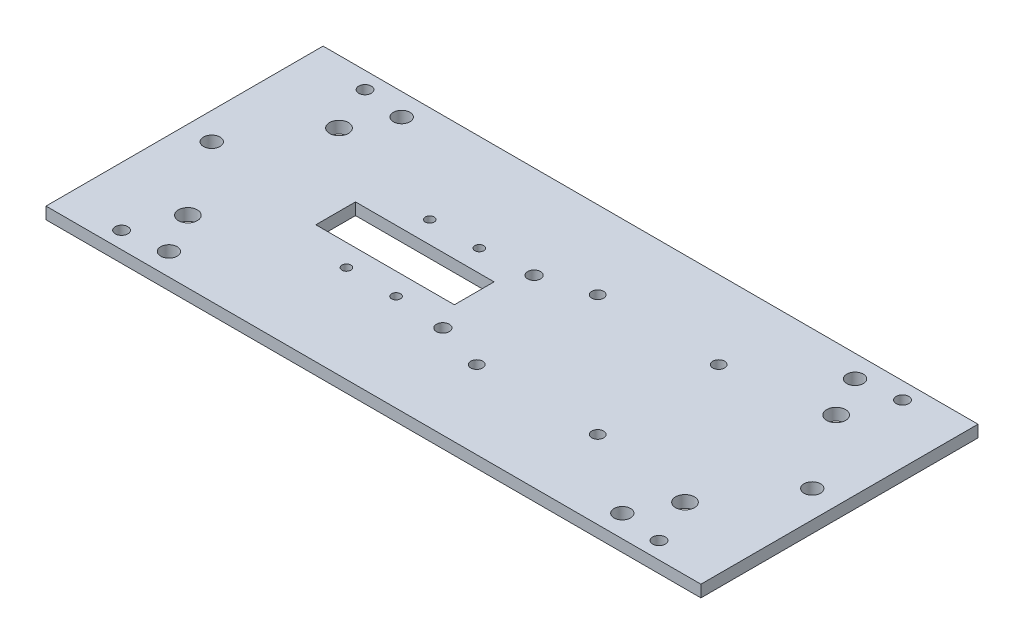
SolidWorks part; units mm, degrees
material "Thornel VCB-20 Carbon Cloth"
ref_plane "Front Plane" through (0, 0, 0) normal (0, 0, 1) x (1, 0, 0)
ref_plane "Top Plane" through (0, 0, 0) normal (0, 1, 0) x (1, 0, 0)
ref_plane "Right Plane" through (0, 0, 0) normal (1, 0, 0) x (0, 0, -1)
sketch "Sketch1" plane through (0, 0, 0) normal (0, 1, 0) x (1, 0, 0)
  line L0 (82.55, -34.925) -> (82.55, 34.925)
  line L1 (82.55, -34.925) -> (-82.55, -34.925)
  line L2 (82.55, 34.925) -> (-82.55, 34.925)
  line L3 (-82.55, -34.925) -> (-82.55, 34.925)
  line L4 (82.55, -34.925) -> (-82.55, 34.925) construction
  line L5 (82.55, 34.925) -> (-82.55, -34.925) construction
  point P1 (0, 0)
  dimension "D1" = 165.1
  dimension "D2" = 69.85
extrude "Boss-Extrude1" add sketch "Sketch1" along normal blind 3
sketch "Sketch6" plane through (0, 0, 0) normal (0, -1, 0) x (1, 0, 0)
  line L0 (-82.55, -34.925) -> (-82.55, 34.925) construction
  line L1 (-44.45, 5) -> (-9.525, 5)
  line L2 (-44.45, 5) -> (-44.45, -5)
  line L3 (-44.45, -5) -> (-9.525, -5)
  line L4 (-9.525, 5) -> (-9.525, -5)
  line L5 (-5.925, -11.501) -> (-63.925, -11.501) construction
  line L6 (-5.925, -11.501) -> (-5.925, 11.501) construction
  line L7 (-5.925, 11.501) -> (-63.925, 11.501) construction
  line L8 (-63.925, -11.501) -> (-63.925, 11.501) construction
  line L9 (-5.925, -11.501) -> (-63.925, 11.501) construction
  line L10 (-5.925, 11.501) -> (-63.925, -11.501) construction
  circle A0 centre (6.35, 15.25) radius 1.5
  circle A1 centre (36.85, 15.25) radius 1.5
  circle A2 centre (6.35, -15.25) radius 1.5
  circle A3 centre (36.85, -15.25) radius 1.5
  circle A4 centre (-63.925, 11.501) radius 1.625 construction
  circle A5 centre (-5.925, 11.501) radius 1.625
  circle A6 centre (-5.925, -11.501) radius 1.625
  circle A7 centre (-63.925, -11.501) radius 1.625 construction
  point P8 (-9.525, 0)
  point P18 (-34.925, 0)
  dimension "D5" = 3
  dimension "D6" = 3
  dimension "D7" = 3
  dimension "D8" = 3
  dimension "D18" = 3.25
  dimension "D1" = 34.925
  dimension "D2" = 10
  dimension "D3" = 38.1
  dimension "D4" = 30.5
  dimension "D9" = 30.5
  dimension "D10" = 30.5
  dimension "D11" = 15.25
  dimension "D12" = 6.35
  dimension "D13" = 15.25
  dimension "D14" = 15.25
  dimension "D15" = 15.25
  dimension "D16" = 23.002
  dimension "D17" = 58
  dimension "D19" = 47.625
  dimension "D20" = 0
extrude "Cut-Extrude1" cut sketch "Sketch6" against normal up to next contours A4 | L4 L1 L2 L3 A4 | A6 | A2 | A3 | A1 | A0 | A7 | A5 region at (-26.9875, 0, 0) region at (6.35, 0, 15.25) region at (36.85, 0, 15.25) region at (6.35, 0, -15.25) region at (36.85, 0, -15.25) region at (-5.925, 0, -11.501)
sketch "Sketch7" plane through (0, 3, 0) normal (0, 1, 0) x (1, 0, 0)
  line L0 (-82.55, 34.925) -> (-82.55, -34.925) construction
  line L1 (82.55, -34.925) -> (82.55, 34.925) construction
  line L2 (-82.55, -34.925) -> (82.55, -34.925) construction
  line L3 (82.55, 34.925) -> (-82.55, 34.925) construction
  circle A0 centre (-77.47, 29.845) radius 1.5
  circle A1 centre (-77.47, -29.845) radius 1.5
  circle A2 centre (77.47, -29.845) radius 1.5
  circle A3 centre (77.47, 29.845) radius 1.5
  dimension "D9" = 3
  dimension "D10" = 3
  dimension "D11" = 3
  dimension "D12" = 3
  dimension "D1" = 5.08
  dimension "D2" = 5.08
  dimension "D3" = 5.08
  dimension "D4" = 5.08
  dimension "D5" = 5.08
  dimension "D6" = 5.08
  dimension "D7" = 5.08
  dimension "D8" = 5.08
sketch "Sketch8" plane through (0, 3, 0) normal (0, 1, 0) x (1, 0, 0)
  line L0 (-82.55, -34.925) -> (82.55, -34.925) construction
  line L1 (-82.55, 34.925) -> (-82.55, -34.925) construction
  line L2 (82.55, -34.925) -> (82.55, 34.925) construction
  line L3 (82.55, 34.925) -> (-82.55, 34.925) construction
  circle A0 centre (-62.6618, -19.05) radius 2.3813
  circle A1 centre (-62.6618, 19.05) radius 2.3813
  circle A2 centre (62.6618, 19.05) radius 2.3813
  circle A3 centre (62.6618, -19.05) radius 2.3813
  dimension "D1" = 4.7625
  dimension "D4" = 4.7625
  dimension "D5" = 4.7625
  dimension "D6" = 4.7625
  dimension "D2" = 15.875
  dimension "D3" = 19.8882
  dimension "D7" = 19.8882
  dimension "D8" = 19.8882
  dimension "D9" = 19.8882
  dimension "D10" = 15.875
  dimension "D11" = 15.875
  dimension "D12" = 15.875
extrude "Cut-Extrude3" cut sketch "Sketch8" against normal up to next
sketch "Sketch9" plane through (0, 3, 0) normal (0, 1, 0) x (1, 0, 0)
  line L0 (-82.55, 34.925) -> (-82.55, -34.925) construction
  line L1 (82.55, -34.925) -> (82.55, 34.925) construction
  circle A0 centre (-75.692, 0) radius 2.0828
  circle A1 centre (75.692, 0) radius 2.0828
  dimension "D1" = 6.858
  dimension "D2" = 6.858
extrude "Cut-Extrude5" cut sketch "Sketch9" against normal blind 5.08
sketch "Sketch10" plane through (0, 3, 0) normal (0, 1, 0) x (1, 0, 0)
  line L0 (-82.55, -34.925) -> (82.55, -34.925) construction
  line L1 (82.55, 34.925) -> (-82.55, 34.925) construction
  circle A0 centre (0, -29.337) radius 2.0828
  circle A1 centre (0, 29.337) radius 2.0828
  circle A2 centre (57.15, -29.337) radius 2.0828
  circle A3 centre (57.15, 29.337) radius 2.0828
  circle A4 centre (-57.15, -29.337) radius 2.0828
  circle A5 centre (-57.15, 29.337) radius 2.0828
  dimension "D1" = 5.588
  dimension "D2" = 5.588
  dimension "D3" = 2
  dimension "D4" = 2
extrude "Cut-Extrude6" cut sketch "Sketch10" against normal blind 5.08 contours A5 | A2 | A3 | A4 region at (57.15, 3, 29.337) region at (57.15, 3, -29.337) region at (-57.15, 3, 29.337) region at (-57.15, 3, -29.337)
sketch "Sketch11" plane through (0, 3, 0) normal (0, 1, 0) x (1, 0, 0)
  line L1 (-18.7375, 10.5) -> (-31.2375, 10.5) construction
  line L2 (-18.7375, 10.5) -> (-18.7375, -10.5) construction
  line L3 (-18.7375, -10.5) -> (-31.2375, -10.5) construction
  line L4 (-31.2375, 10.5) -> (-31.2375, -10.5) construction
  line L5 (-18.7375, 10.5) -> (-31.2375, -10.5) construction
  line L6 (-18.7375, -10.5) -> (-31.2375, 10.5) construction
  line L7 (-9.525, 5) -> (-44.45, 5) construction
  circle A0 centre (-31.2375, 10.5) radius 1.125
  circle A1 centre (-18.7375, 10.5) radius 1.125
  circle A2 centre (-18.7375, -10.5) radius 1.125
  circle A3 centre (-31.2375, -10.5) radius 1.125
  point P0 (-24.9875, 0)
  point P9 (-26.9875, 5)
  dimension "D4" = 2.25
  dimension "D5" = 2.25
  dimension "D6" = 2.25
  dimension "D7" = 2.25
  dimension "D1" = 12.5
  dimension "D2" = 21
  dimension "D3" = 2
extrude "Cut-Extrude7" cut sketch "Sketch11" against normal blind 41.91
sketch "Sketch12" plane through (0, 0, 0) normal (0, -1, 0) x (1, 0, 0)
  line L0 (-24.5963, 23.3735) -> (-5.5463, 23.3735) construction
  line L1 (-24.5963, 24.5641) -> (-5.5463, 24.5641)
  line L2 (-24.5963, 24.5641) -> (-24.5963, 22.1829)
  line L3 (-24.5963, 22.1829) -> (-5.5463, 22.1829)
  line L4 (-5.5463, 24.5641) -> (-5.5463, 22.1829)
  line L5 (-15.0713, 24.5641) -> (-15.0713, 22.1829)
  line L6 (0.8037, 24.5641) -> (0.8037, 22.1829)
  line L7 (0.8037, 24.5641) -> (19.8537, 24.5641)
  line L8 (19.8537, 24.5641) -> (19.8537, 22.1829)
  line L9 (0.8037, 22.1829) -> (19.8537, 22.1829)
  line L10 (26.2037, 24.5641) -> (26.2037, 22.1829)
  line L11 (26.2037, 24.5641) -> (45.2537, 24.5641)
  line L12 (45.2537, 24.5641) -> (45.2537, 22.1829)
  line L13 (26.2037, 22.1829) -> (45.2537, 22.1829)
  line L14 (0.8037, 9.3241) -> (0.8037, 6.9429)
  line L15 (0.8037, 9.3241) -> (19.8537, 9.3241)
  line L16 (19.8537, 9.3241) -> (19.8537, 6.9429)
  line L17 (0.8037, 6.9429) -> (19.8537, 6.9429)
  line L18 (26.2037, 9.3241) -> (26.2037, 6.9429)
  line L19 (26.2037, 9.3241) -> (45.2537, 9.3241)
  line L20 (45.2537, 9.3241) -> (45.2537, 6.9429)
  line L21 (26.2037, 6.9429) -> (45.2537, 6.9429)
  line L22 (-24.5963, 9.3241) -> (-24.5963, 6.9429)
  line L23 (-24.5963, 9.3241) -> (-5.5463, 9.3241)
  line L24 (-5.5463, 9.3241) -> (-5.5463, 6.9429)
  line L25 (-24.5963, 6.9429) -> (-5.5463, 6.9429)
  line L26 (-24.5963, 24.5641) -> (0.8037, 24.5641) construction
  line L27 (-71.2714, 9.2531) -> (-61.3765, 9.2531)
  line L28 (-24.5963, -24.8071) -> (0.8037, -24.8071) construction
  line L29 (-24.5963, -23.6165) -> (-5.5463, -23.6165) construction
  line L30 (-24.5963, -7.1859) -> (-5.5463, -7.1859)
  line L31 (-5.5463, -9.5671) -> (-5.5463, -7.1859)
  line L32 (-24.5963, -9.5671) -> (-5.5463, -9.5671)
  line L33 (-24.5963, -9.5671) -> (-24.5963, -7.1859)
  line L34 (26.2037, -7.1859) -> (45.2537, -7.1859)
  line L35 (45.2537, -9.5671) -> (45.2537, -7.1859)
  line L36 (26.2037, -9.5671) -> (45.2537, -9.5671)
  line L37 (26.2037, -9.5671) -> (26.2037, -7.1859)
  line L38 (0.8037, -7.1859) -> (19.8537, -7.1859)
  line L39 (19.8537, -9.5671) -> (19.8537, -7.1859)
  line L40 (0.8037, -9.5671) -> (19.8537, -9.5671)
  line L41 (0.8037, -9.5671) -> (0.8037, -7.1859)
  line L42 (26.2037, -22.4259) -> (45.2537, -22.4259)
  line L43 (45.2537, -24.8071) -> (45.2537, -22.4259)
  line L44 (26.2037, -24.8071) -> (45.2537, -24.8071)
  line L45 (26.2037, -24.8071) -> (26.2037, -22.4259)
  line L46 (0.8037, -22.4259) -> (19.8537, -22.4259)
  line L47 (19.8537, -24.8071) -> (19.8537, -22.4259)
  line L48 (0.8037, -24.8071) -> (19.8537, -24.8071)
  line L49 (0.8037, -24.8071) -> (0.8037, -22.4259)
  line L50 (-15.0713, -24.8071) -> (-15.0713, -22.4259)
  line L51 (-5.5463, -24.8071) -> (-5.5463, -22.4259)
  line L52 (-24.5963, -22.4259) -> (-5.5463, -22.4259)
  line L53 (-24.5963, -24.8071) -> (-24.5963, -22.4259)
  line L54 (-24.5963, -24.8071) -> (-5.5463, -24.8071)
  line L56 (-3.1651, 10.991) -> (-1.5776, 10.991)
  line L57 (-3.1651, 10.991) -> (-3.1651, 20.516)
  line L58 (-3.1651, 20.516) -> (-1.5776, 20.516)
  line L59 (-1.5776, 10.991) -> (-1.5776, 20.516)
  line L60 (-3.1651, 10.991) -> (-1.5776, 20.516) construction
  line L61 (-3.1651, 20.516) -> (-1.5776, 10.991) construction
  line L66 (-3.1651, -20.759) -> (-1.5776, -20.759)
  line L67 (-1.5776, -11.234) -> (-1.5776, -20.759)
  line L68 (-3.1651, -11.234) -> (-1.5776, -11.234)
  line L69 (-3.1651, -11.234) -> (-3.1651, -20.759)
  line L78 (51.6896, 8.9006) -> (51.6896, 6.5194)
  line L79 (51.6896, 8.9006) -> (70.7396, 8.9006)
  line L80 (70.7396, 8.9006) -> (70.7396, 6.5194)
  line L81 (51.6896, 6.5194) -> (70.7396, 6.5194)
  line L82 (-70.3121, -11.1231) -> (-60.4172, -11.1231)
  line L83 (64.3896, -0.545) -> (-18.1604, -0.545) construction
  line L84 (-70.3121, -11.1231) -> (-70.3121, -9.3903)
  line L85 (51.6896, -7.6094) -> (70.7396, -7.6094)
  line L86 (70.7396, -9.9906) -> (70.7396, -7.6094)
  line L87 (51.6896, -9.9906) -> (70.7396, -9.9906)
  line L88 (51.6896, -9.9906) -> (51.6896, -7.6094)
  line L93 (73.1208, 10.5675) -> (73.1208, 20.0925)
  line L94 (47.7208, 10.5675) -> (49.3083, 10.5675)
  line L95 (47.7208, 10.5675) -> (47.7208, 20.0925)
  line L96 (47.7208, 20.0925) -> (49.3083, 20.0925)
  line L97 (49.3083, 10.5675) -> (49.3083, 20.0925)
  line L98 (47.7208, 10.5675) -> (49.3083, 20.0925) construction
  line L99 (47.7208, 20.0925) -> (49.3083, 10.5675) construction
  line L100 (73.1208, 10.5675) -> (74.7083, 10.5675)
  line L101 (74.7083, 10.5675) -> (74.7083, 20.0925)
  line L102 (73.1208, 20.0925) -> (74.7083, 20.0925)
  line L103 (47.7208, 10.5675) -> (73.1208, 10.5675) construction
  line L104 (47.7208, -21.1825) -> (49.3083, -21.1825)
  line L105 (49.3083, -11.6575) -> (49.3083, -21.1825)
  line L106 (47.7208, -11.6575) -> (49.3083, -11.6575)
  line L107 (47.7208, -11.6575) -> (47.7208, -21.1825)
  line L108 (73.1208, -11.6575) -> (74.7083, -11.6575)
  line L109 (74.7083, -11.6575) -> (74.7083, -21.1825)
  line L110 (73.1208, -21.1825) -> (74.7083, -21.1825)
  line L111 (73.1208, -11.6575) -> (73.1208, -21.1825)
  line L112 (-70.3121, -9.3903) -> (-60.4172, -9.3903)
  line L113 (-60.4172, -11.1231) -> (-60.4172, -9.3903)
  line L114 (-52.8291, -27.8715) -> (-33.7791, -27.8715)
  line L115 (-33.7791, -30.2527) -> (-33.7791, -27.8715)
  line L116 (-52.8291, -30.2527) -> (-33.7791, -30.2527)
  line L117 (-52.8291, -30.2527) -> (-52.8291, -27.8715)
  line L118 (-70.3121, -11.1231) -> (-60.4172, -9.3903) construction
  line L123 (-59.3265, -23.1262) -> (-57.739, -23.1262)
  line L124 (-57.739, -13.6012) -> (-57.739, -23.1262)
  line L125 (-59.3265, -13.6012) -> (-57.739, -13.6012)
  line L126 (-59.3265, -13.6012) -> (-59.3265, -23.1262)
  line L127 (-31.3979, -16.6796) -> (-29.8104, -16.6796)
  line L128 (-29.8104, -16.6796) -> (-29.8104, -26.2046)
  line L129 (-31.3979, -26.2046) -> (-29.8104, -26.2046)
  line L130 (-31.3979, -16.6796) -> (-31.3979, -26.2046)
  line L131 (-70.3121, -9.3903) -> (-60.4172, -11.1231) construction
  line L132 (-71.2714, 9.2531) -> (-71.2714, 10.9859)
  line L133 (-31.3979, 16.4366) -> (-31.3979, 25.9616)
  line L134 (-31.3979, 25.9616) -> (-29.8104, 25.9616)
  line L135 (-29.8104, 16.4366) -> (-29.8104, 25.9616)
  line L136 (-31.3979, 16.4366) -> (-29.8104, 16.4366)
  line L137 (-59.5464, 13.798) -> (-59.5464, 23.323)
  line L138 (-59.5464, 13.798) -> (-57.9589, 13.798)
  line L139 (-57.9589, 13.798) -> (-57.9589, 23.323)
  line L140 (-59.5464, 23.323) -> (-57.9589, 23.323)
  line L145 (-71.2714, 10.9859) -> (-61.3765, 10.9859)
  line L146 (-52.8291, 30.0097) -> (-52.8291, 27.6285)
  line L147 (-52.8291, 30.0097) -> (-33.7791, 30.0097)
  line L148 (-33.7791, 30.0097) -> (-33.7791, 27.6285)
  line L149 (-52.8291, 27.6285) -> (-33.7791, 27.6285)
  line L150 (-61.3765, 9.2531) -> (-61.3765, 10.9859)
  point P8 (-65.3646, -10.2567)
  point P60 (-2.3713, 15.7535)
  point P100 (48.5146, 15.33)
  dimension "D1" = 19.05
  dimension "D2" = 2.3813
  dimension "D3" = 25.4
  dimension "D4" = 15.24
  dimension "D5" = 1.5875
  dimension "D6" = 3.175
  dimension "D7" = 9.525
  dimension "D8" = 7.62
extrude "Cut-Extrude8" [suppressed] cut sketch "Sketch12" against normal blind 21.336 contours L37 L36 L35 L34 | L88 L87 L86 L85 | L45 L44 L43 L42 | L117 L116 L115 L114 | L78 L81 L80 L79 | L10 L13 L12 L11 | L6 L9 L8 L7 | L14 L17 L16 L15 | L107 L104 L105 L106 | L109 L110 L111 L108 | L40 L39 L38 L41 | L48 L47 L46 L49 | L67 L66 L69 L68 | L52 L51 L54 L53 | L30 L31 L32 L33 | L130 L129 L128 L127 | L126 L123 L124 L125 | L93 L102 L101 L100 | L97 L96 L95 L94 | L19 L20 L21 L18 | L56 L59 L58 L57 | L25 L24 L23 L22 | L3 L4 L1 L2 | L135 L134 L133 L136 | L149 L148 L147 L146 | L139 L140 L137 L138 | L27 L150 L145 L132 | L84 L82 L113 L112
sketch "Sketch13" plane through (0, 0, 0) normal (0, -1, 0) x (1, 0, 0)
  line L2 (-82.55, 34.925) -> (82.55, 34.925) construction
  circle A0 centre (-62.6618, 19.05) radius 2.3813 construction
  circle A6 centre (-67.7422, 30.6896) radius 1.5875
  circle A12 centre (67.7422, 30.6896) radius 1.5875
  circle A15 centre (67.7422, -30.6896) radius 1.5875
  circle A16 centre (-67.7422, -30.6896) radius 1.5875
  point P13 (0, 0)
  point P17 (0.9735, -0.4356)
  point P19 (-0.1369, 0.0621)
  dimension "D2" = 3.175
  dimension "D1" = 12.7
  dimension "D3" = 2
  dimension "D4" = 4.2354
extrude "Cut-Extrude9" cut sketch "Sketch13" against normal blind 5
